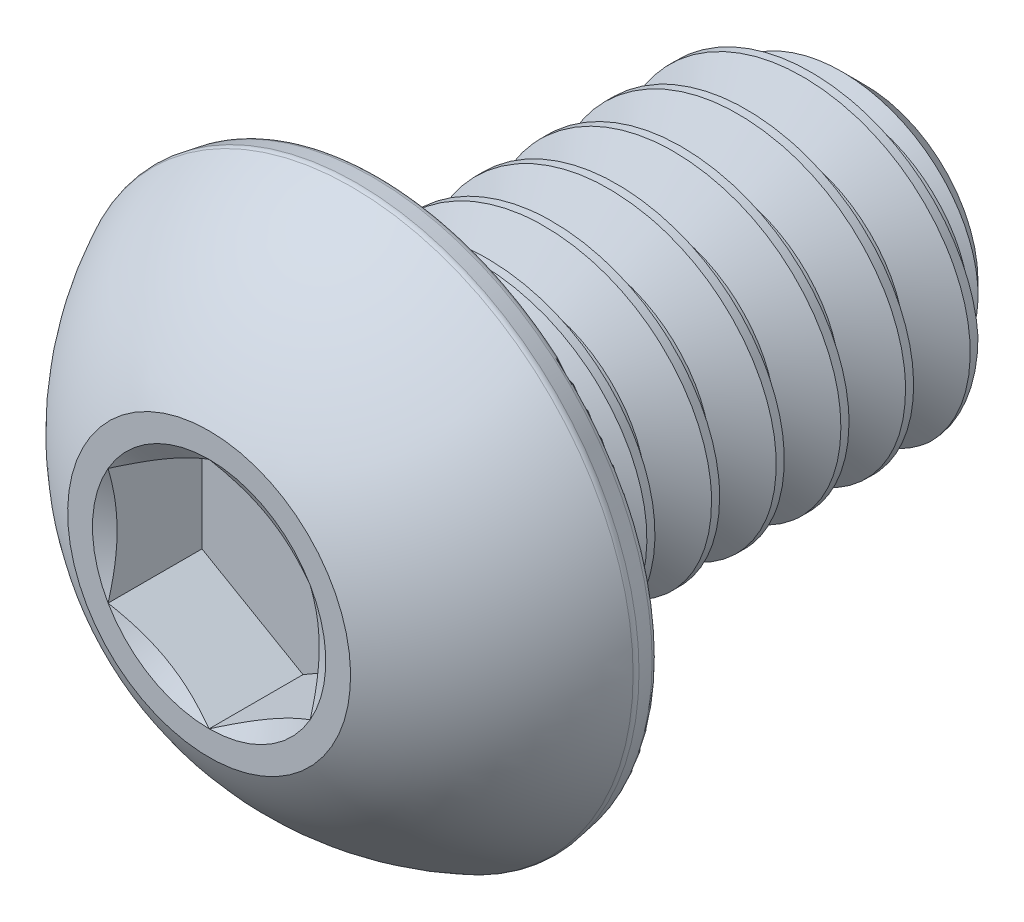
SolidWorks part; units mm, degrees
ref_plane "Front Plane" through (0, 0, 0) normal (0, 0, 1) x (1, 0, 0)
ref_plane "Top Plane" through (0, 0, 0) normal (0, 1, 0) x (1, 0, 0)
ref_plane "Right Plane" through (0, 0, 0) normal (1, 0, 0) x (0, 0, -1)
sketch "Sketch1" plane through (0, 0, 0) normal (1, 0, 0) x (0, 0, -1)
  line L0 (-6.4389, 0) -> (6.4389, 0) construction
  line L1 (-6.4389, 0) -> (-6.4389, 5.5499)
  line L2 (-6.4389, 5.5499) -> (-3.0861, 5.5499)
  line L3 (-3.0861, 5.5499) -> (-3.0861, 3.175)
  line L4 (-3.0861, 3.175) -> (6.4389, 3.175)
  line L5 (6.4389, 3.175) -> (6.4389, 0)
  point P2 (0, 0)
  point P4 (5.1689, 0)
  point P9 (4.5339, 3.175)
  point P10 (4.5339, -3.175)
  point P11 (6.4389, -3.175)
  point P15 (-4.5949, 0)
  dimension "Head Height" = 3.3528
  dimension "Head Diameter" = 11.0998
  dimension "Length" = 9.525
  dimension "Screw Size Decimal Equivalent" = 6.35
  dimension "Thread Pitch" = 1.27
  dimension "D1" = 1.905
  dimension "D2" = 1.844
sketch "Sketch2" plane through (0, 0, 0) normal (0, 0, 1) x (1, 0, 0)
  line L0 (0, 3.175) -> (0, 0) construction
  line L1 (0, 2.2914) -> (-1.9844, 1.1457)
  line L2 (-1.9844, 1.1457) -> (-1.9844, -1.1457)
  line L3 (-1.9844, -1.1457) -> (0, -2.2914)
  line L4 (0, -2.2914) -> (1.9844, -1.1457)
  line L5 (1.9844, -1.1457) -> (1.9844, 1.1457)
  line L6 (1.9844, 1.1457) -> (0, 2.2914)
  circle A0 centre (0, 0) radius 1.9844 construction
  circle A1 centre (0, 0) radius 2.7781
  point P10 (0, 2.7781)
  dimension "D1" = 5.5563
  dimension "Drive Size" = 3.9688
sketch "Sketch3" plane through (0, 0, 0) normal (1, 0, 0) x (0, 0, -1)
  line L0 (-6.4389, 0) -> (-6.4389, 2.7781)
  line L1 (-6.4389, 0) -> (-6.4389, 5.5499) construction
  line L2 (-6.4389, 5.5499) -> (-3.0861, 5.5499) construction
  line L3 (-3.589, 5.5499) -> (-3.0861, 5.4612)
  line L4 (-3.0861, 5.5499) -> (-3.0861, 3.175) construction
  line L5 (-3.0861, 5.4612) -> (-3.0861, 3.175)
  line L6 (-6.4389, 0) -> (6.4389, 0) construction
  line L7 (-6.4389, 0) -> (6.4389, 0)
  line L8 (6.4389, 0) -> (6.4389, 2.2225)
  line L9 (6.4389, 3.175) -> (6.4389, 0) construction
  line L10 (6.4389, 2.2225) -> (5.4864, 3.175)
  line L11 (-3.0861, 3.175) -> (6.4389, 3.175) construction
  line L12 (5.4864, 3.175) -> (-3.0861, 3.175)
  arc A0 (-6.4389, 2.7781) -> (-3.589, 5.5499) centre (-0.9641, 0) cw
  dimension "D1" = 0.5029
  dimension "D2" = 10
  dimension "D3" = 45
  dimension "D4" = 0.9525
revolve "Revolve1" add sketch "Sketch3" angle 360 about L7
sketch "Sketch4" plane through (0, 0, 6.4389) normal (0, 0, 1) x (1, 0, 0)
  line L0 (-1.9844, -1.1457) -> (0, -2.2914) construction
  line L1 (-1.9844, 1.1457) -> (-1.9844, -1.1457) construction
  line L2 (0, 2.2914) -> (-1.9844, 1.1457) construction
  line L3 (1.9844, 1.1457) -> (0, 2.2914) construction
  line L4 (1.9844, -1.1457) -> (1.9844, 1.1457) construction
  line L5 (0, -2.2914) -> (1.9844, -1.1457) construction
  line L6 (-1.9844, -1.1457) -> (0, -2.2914)
  line L7 (-1.9844, 1.1457) -> (-1.9844, -1.1457)
  line L8 (0, 2.2914) -> (-1.9844, 1.1457)
  line L9 (1.9844, 1.1457) -> (0, 2.2914)
  line L10 (1.9844, -1.1457) -> (1.9844, 1.1457)
  line L11 (0, -2.2914) -> (1.9844, -1.1457)
extrude "Cut-Extrude1" cut sketch "Sketch4" against normal up to vertex (1.844 mm away) up to point (0, 0, 4.5949)
sketch "Sketch5" plane through (0, 0, 6.4389) normal (0, 0, 1) x (1, 0, 0)
  circle A0 centre (0, 0) radius 2.2914
extrude "Cut-Extrude2" cut sketch "Sketch5" against normal up to vertex (1.844 mm away) draft 60 up to point (0, 0, 4.5949)
fillet "Fillet1" radius 0.1676 2 edges at (5.5499, 0, 3.589) (5.4612, 0, 3.0861)
split "Split1" bodies to split 106 resulting bodies 107 108 split by face at (5.3206, 0, 3.0861)
sketch "Sketch6" plane through (0, 0, -6.4389) normal (0, 0, -1) x (-1, 0, 0)
  circle A0 centre (0, 0) radius 3.175 construction
  circle A1 centre (0, 0) radius 3.175
curve "Helix/Spiral1" pitch 1.27 height 10.795 radius 3.175 centre (0, 0, -6.4389) axis (0, 0, 1) start towards (0, 1, 0)
sketch "Sketch7" plane through (0, 0, 0) normal (1, 0, 0) x (0, 0, -1)
  line L0 (6.3595, 3.3125) -> (6.9945, 2.2126) construction
  line L1 (6.9945, 2.2126) -> (7.6295, 3.3125) construction
  line L2 (7.6295, 3.3125) -> (6.3595, 3.3125) construction
  line L3 (6.3992, 3.2437) -> (7.5898, 3.2437)
  line L4 (7.5898, 3.2437) -> (7.0739, 2.3501)
  line L5 (7.0739, 2.3501) -> (6.9152, 2.3501)
  line L6 (6.9152, 2.3501) -> (6.3992, 3.2437)
  line L7 (6.9945, 2.3501) -> (6.9945, 2.2126) construction
  line L8 (6.4389, 3.175) -> (7.5502, 3.175) construction
  line L9 (6.9945, 3.3125) -> (6.9945, 3.175) construction
  point P12 (6.9945, 3.2437)
  dimension "D1" = 1.27
  dimension "D2" = 0.1588
sweep "Cut-Sweep1" cut profiles "Sketch7" path "Helix/Spiral1" align with end faces yes
sketch "Sketch8" plane through (0, 0, 3.0861) normal (0, 0, -1) x (-1, 0, 0)
  circle A0 centre (0, 0) radius 3.3125
extrude "Boss-Extrude1" add sketch "Sketch8" along normal up to vertex (7.62 mm away) draft 45 up to point (0, 3.175, -4.5339)
equation "\"D1@Sketch1\"=\"Thread Pitch@Sketch1\"*1.5"
equation "\"D2@Sketch1\"=0.55*\"Head Height@Sketch1\""
equation "\"D1@Sketch2\"=\"Drive Size@Sketch2\"*1.4"
equation "\"D1@Sketch3\"=0.15*\"Head Height@Sketch1\""
equation "\"D4@Sketch3\"=0.75*\"Thread Pitch@Sketch1\""
equation "\"D1@Fillet1\"=.05*\"Head Height@Sketch1\""
equation "\"D4@Helix/Spiral1\"=\"Thread Pitch@Sketch1\""
equation "\"D3@Helix/Spiral1\"=\"Length@Sketch1\"+\"Thread Pitch@Sketch1\""
equation "\"D2@Sketch7\"=\"D1@Sketch7\"/8"
equation "\"D1@Sketch7\"=\"Thread Pitch@Sketch1\""
